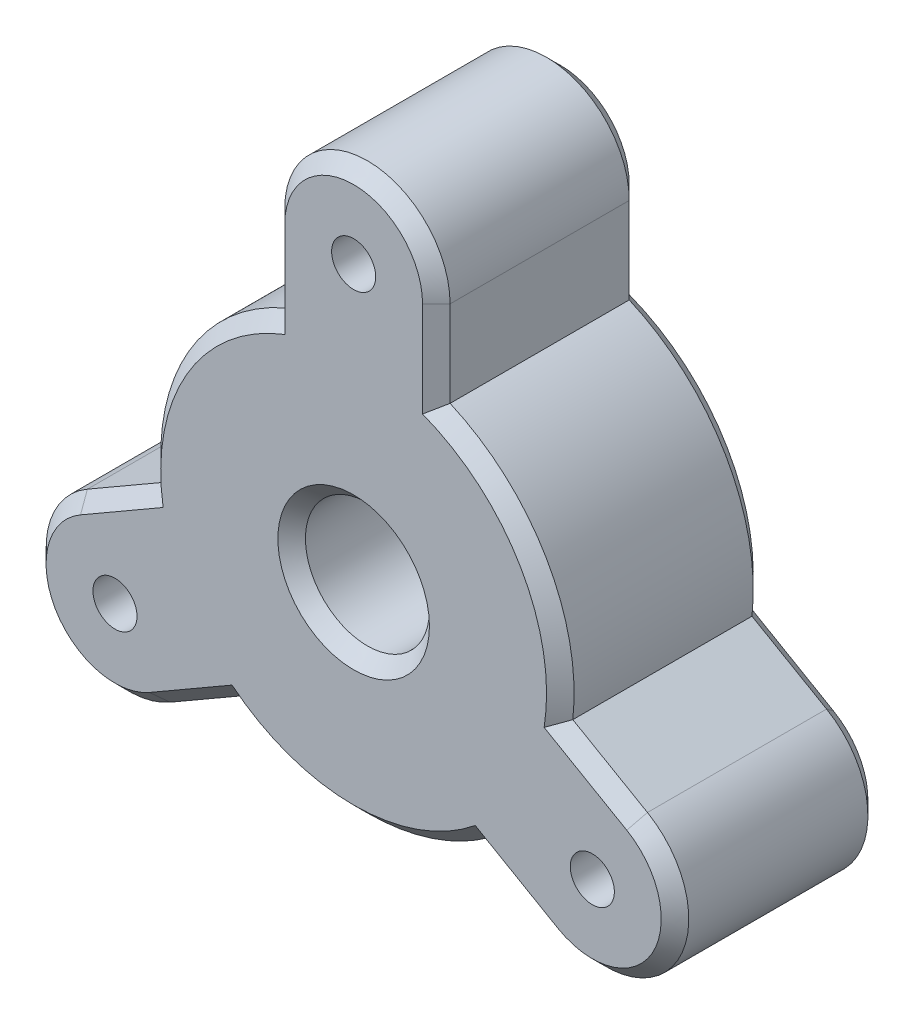
SolidWorks part; units mm, degrees
material "ABS"
ref_plane "Front Plane" through (0, 0, 0) normal (0, 0, 1) x (1, 0, 0)
ref_plane "Top Plane" through (0, 0, 0) normal (0, 1, 0) x (1, 0, 0)
ref_plane "Right Plane" through (0, 0, 0) normal (1, 0, 0) x (0, 0, -1)
sketch "Sketch1" plane through (0, 0, 0) normal (0, 0, 1) x (1, 0, 0)
  circle A0 centre (0, 0) radius 15
  dimension "D1" = 30
sketch "Sketch2" plane through (0, 0, 0) normal (0, 0, 1) x (1, 0, 0)
  line L0 (0, 0) -> (0, 20) construction
  line L1 (-6, 20) -> (6, 20) construction
  line L2 (-6, 20) -> (-6, 13.7477)
  line L3 (6, 20) -> (6, 13.7477)
  line L4 (-6, 13.7477) -> (6, 13.7477)
  line L5 (20.3205, -4.8038) -> (14.9059, -1.6777)
  line L6 (14.3205, -15.1962) -> (8.9059, -12.07)
  line L7 (14.9059, -1.6777) -> (8.9059, -12.07)
  line L8 (20.3205, -4.8038) -> (14.3205, -15.1962) construction
  line L9 (-14.3205, -15.1962) -> (-8.9059, -12.07)
  line L10 (-20.3205, -4.8038) -> (-14.9059, -1.6777)
  line L11 (-8.9059, -12.07) -> (-14.9059, -1.6777)
  line L12 (-14.3205, -15.1962) -> (-20.3205, -4.8038) construction
  circle A0 centre (0, 0) radius 15 construction
  arc A2 (6, 20) -> (-6, 20) centre (0, 20) ccw
  arc A3 (14.3205, -15.1962) -> (20.3205, -4.8038) centre (17.3205, -10) ccw
  arc A4 (-20.3205, -4.8038) -> (-14.3205, -15.1962) centre (-17.3205, -10) ccw
  point P5 (0, 20)
  point P22 (0, 0)
  dimension "D1" = 12
  dimension "D2" = 20
  dimension "D3" = 3
sketch "Sketch3" plane through (0, 0, 0) normal (0, 0, 1) x (1, 0, 0)
  circle A0 centre (0, 0) radius 4.5
  dimension "D1" = 9
extrude "Boss-Extrude1" add sketch "Sketch1" along normal mid plane 15
extrude "Boss-Extrude2" add sketch "Sketch2" along normal up to surface and the other way up to surface up to face at (15, 0, 7.5) other way up to face at (15, 0, -7.5)
extrude "Cut-Extrude1" cut sketch "Sketch3" along normal through all and the other way through all
chamfer "Chamfer1" distance 1 angle 45 26 edges at (4.5, 0, 7.5) (-6, 16.8739, 7.5) (0, 26, 7.5) (6, 16.8739, 7.5) (12.9904, 7.5, 7.5) (17.6132, -3.2408, 7.5) (22.5167, -13, 7.5) (11.6132, -13.6331, 7.5) (0, -15, 7.5) (-11.6132, -13.6331, 7.5) (-22.5167, -13, 7.5) (-17.6132, -3.2408, 7.5) (-12.9904, 7.5, 7.5) (4.5, 0, -7.5) (11.6132, -13.6331, -7.5) (22.5167, -13, -7.5) (17.6132, -3.2408, -7.5) (12.9904, 7.5, -7.5) (6, 16.8739, -7.5) (0, 26, -7.5) (-6, 16.8739, -7.5) (-12.9904, 7.5, -7.5) (-17.6132, -3.2408, -7.5) (-22.5167, -13, -7.5) (-11.6132, -13.6331, -7.5) (0, -15, -7.5)
sketch "Sketch4" plane through (0, 0, 0) normal (0, 0, 1) x (1, 0, 0)
  circle A0 centre (0, 20) radius 1.6
  circle A1 centre (17.3205, -10) radius 1.6
  circle A2 centre (-17.3205, -10) radius 1.6
  arc A3 (-14.3205, -15.1962) -> (-20.3205, -4.8038) centre (-17.3205, -10) ccw construction
  arc A4 (-6, 20) -> (6, 20) centre (0, 20) ccw construction
  arc A5 (20.3205, -4.8038) -> (14.3205, -15.1962) centre (17.3205, -10) ccw construction
  dimension "D1" = 3.2
extrude "Cut-Extrude2" cut sketch "Sketch4" along normal through all and the other way through all
